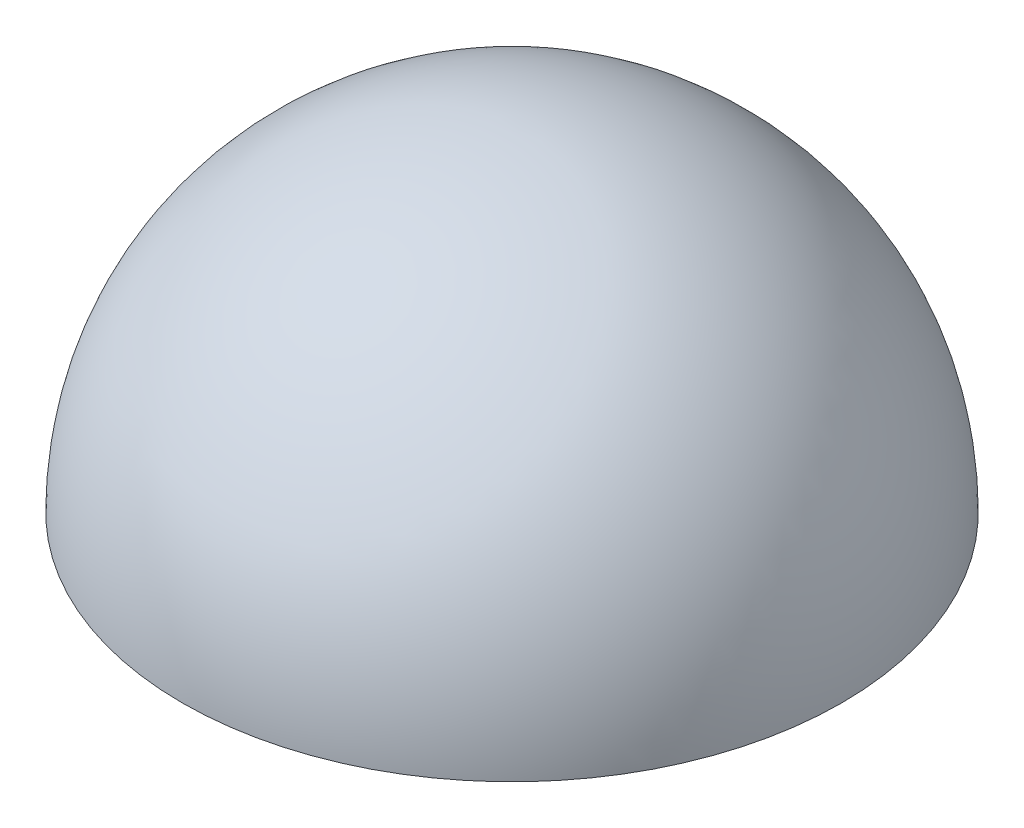
SolidWorks part; units mm, degrees
material "Rubber"
ref_plane "Front Plane" through (0, 0, 0) normal (0, 0, 1) x (1, 0, 0)
ref_plane "Top Plane" through (0, 0, 0) normal (0, 1, 0) x (1, 0, 0)
ref_plane "Right Plane" through (0, 0, 0) normal (1, 0, 0) x (0, 0, -1)
sketch "Sketch1" plane through (0, 0, 0) normal (0, 0, 1) x (1, 0, 0)
  line L0 (0, 0) -> (0, 12.7)
  line L1 (-12.7, 0) -> (0, 0)
  line L2 (0, 0) -> (0, 0.0519)
  arc A0 (0, 12.7) -> (-12.7, 0) centre (0, 0) ccw
  dimension "D1" = 12.7
revolve "Revolve1" add sketch "Sketch1" angle 360 about L0 region at (-5.39, 5.39, 0)
ref_axis "Axis1" through (0, 13.335, 0) along (0, -1, 0)
ref_point "fingertip"
